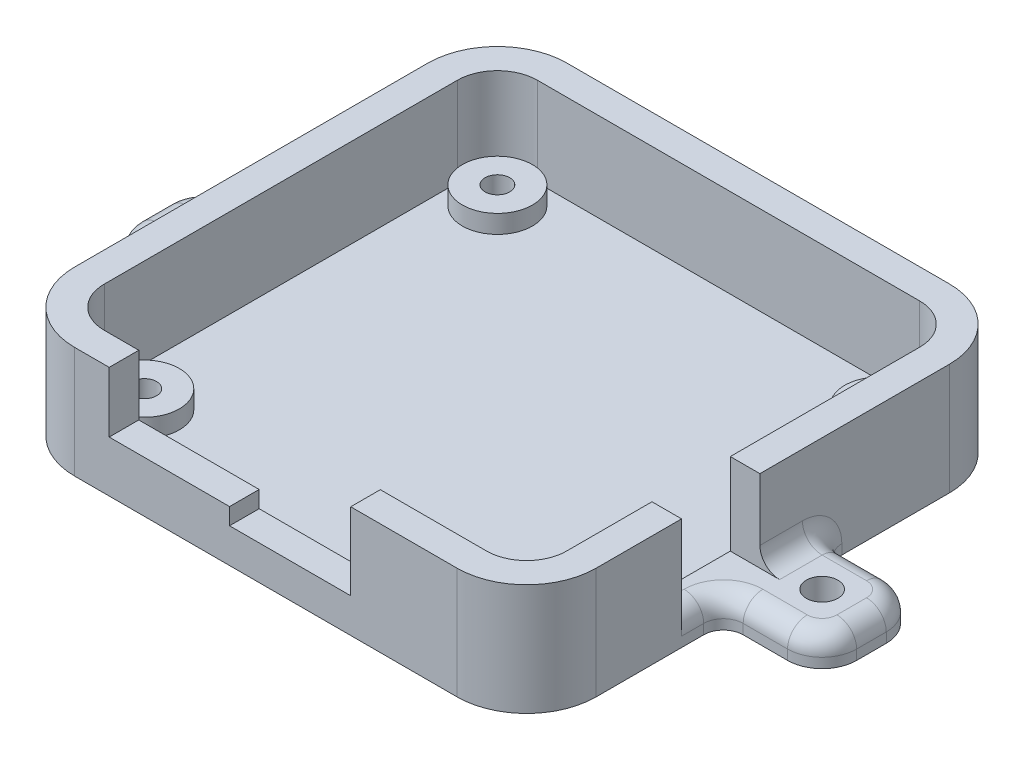
SolidWorks part; units mm, degrees
ref_plane "Front Plane" through (0, 0, 0) normal (0, 0, 1) x (1, 0, 0)
ref_plane "Top Plane" through (0, 0, 0) normal (0, 1, 0) x (1, 0, 0)
ref_plane "Right Plane" through (0, 0, 0) normal (1, 0, 0) x (0, 0, -1)
sketch "Sketch1" plane through (0, 0, 0) normal (0, 1, 0) x (1, 0, 0)
  line L0 (3.556, 0.5) -> (42.304, 0.5)
  line L1 (3.556, 0) -> (42.304, 0)
  line L2 (0, -3.556) -> (0, -39.344)
  line L3 (3.556, -42.9) -> (42.304, -42.9)
  line L4 (45.86, -3.556) -> (45.86, -39.344)
  line L5 (46.36, -3.556) -> (46.36, -39.344)
  line L6 (3.556, -43.4) -> (42.304, -43.4)
  line L7 (-0.5, -3.556) -> (-0.5, -39.344)
  line L8 (3.556, 3.5) -> (42.304, 3.5)
  line L9 (49.36, -3.556) -> (49.36, -39.344)
  line L10 (3.556, -46.4) -> (42.304, -46.4)
  line L11 (-3.5, -3.556) -> (-3.5, -39.344)
  arc A0 (42.304, 0) -> (45.86, -3.556) centre (42.304, -3.556) cw
  arc A1 (45.86, -39.344) -> (42.304, -42.9) centre (42.304, -39.344) cw
  arc A2 (3.556, -42.9) -> (0, -39.344) centre (3.556, -39.344) cw
  arc A3 (0, -3.556) -> (3.556, 0) centre (3.556, -3.556) cw
  circle A4 centre (3.556, -3.556) radius 1.25
  circle A5 centre (42.304, -3.556) radius 1.25
  circle A6 centre (42.304, -39.344) radius 1.25
  circle A7 centre (3.556, -39.344) radius 1.25
  arc A8 (42.304, 0.5) -> (46.36, -3.556) centre (42.304, -3.556) cw
  arc A9 (46.36, -39.344) -> (42.304, -43.4) centre (42.304, -39.344) cw
  arc A10 (3.556, -43.4) -> (-0.5, -39.344) centre (3.556, -39.344) cw
  arc A11 (-0.5, -3.556) -> (3.556, 0.5) centre (3.556, -3.556) cw
  arc A12 (42.304, 3.5) -> (49.36, -3.556) centre (42.304, -3.556) cw
  arc A13 (49.36, -39.344) -> (42.304, -46.4) centre (42.304, -39.344) cw
  arc A14 (3.556, -46.4) -> (-3.5, -39.344) centre (3.556, -39.344) cw
  arc A15 (-3.5, -3.556) -> (3.556, 3.5) centre (3.556, -3.556) cw
  circle A16 centre (3.556, -3.556) radius 3.55
  circle A17 centre (42.304, -3.556) radius 3.55
  circle A18 centre (42.304, -39.344) radius 3.55
  circle A19 centre (3.556, -39.344) radius 3.55
  point P8 (45.86, 0)
  point P13 (0, -42.9)
  point P16 (0, 0)
  dimension "D3" = 3.556
  dimension "D4" = 2.5
  dimension "D5" = 2.5
  dimension "D6" = 2.5
  dimension "D7" = 2.5
  dimension "D1" = 42.9
  dimension "D2" = 45.86
  dimension "D8" = 0.5
  dimension "D9" = 3
  dimension "D10" = 2.3
extrude "Boss-Extrude1" add sketch "Sketch1" along normal blind 2.3 contours A15 L11 A14 L10 A13 L9 A12 L8 L7 A11 L0 A8 L5 A9 L6 A10 | A11 L7 A10 L6 A9 L5 A8 L0 L2 A3 L1 A0 L4 A1 L3 A2 | A3 L2 A2 L3 A1 L4 A0 L1 A19 A18 A17 A16 | A18 A6 | A19 A7 | A16 A4 | A17 A5 region at (22.93, 0, -0.4358) region at (22.93, 0, 21.45) region at (22.93, 0, -2.7731) region at (0.1064, 0, 3.556) region at (38.8544, 0, 3.556) region at (38.8544, 0, 39.344) region at (0.1064, 0, 39.344)
extrude "Boss-Extrude2" add sketch "Sketch1<3>" along normal blind 1.85 from surface contours A16 A4 | A17 A5 | A18 A6 | A19 A7 region at (0.1064, 0, 3.556) region at (38.8544, 0, 3.556) region at (38.8544, 0, 39.344) region at (0.1064, 0, 39.344) starting at face at (22.93, 2.3, 21.45)
sketch "Sketch1<3>" plane through (0, 0, 0) normal (0, 1, 0) x (1, 0, 0) same geometry as "Sketch1"
extrude "Boss-Extrude3" add sketch "Sketch1<4>" along normal blind 9 from surface contours A15 L11 A14 L10 A13 L9 A12 L8 L7 A11 L0 A8 L5 A9 L6 A10 region at (22.93, 0, -2.7731) starting at face at (42.304, 2.3, 42.894)
sketch "Sketch1<4>" plane through (0, 0, 0) normal (0, 1, 0) x (1, 0, 0) same geometry as "Sketch1"
sketch "Sketch2" plane through (49.36, 0, 0) normal (1, 0, 0) x (0, 0, -1)
  line L0 (-3.556, 0) -> (-39.344, 0) construction
  line L1 (-30.694, 11.3) -> (-22.756, 11.3)
  line L2 (-30.694, 11.3) -> (-30.694, 3)
  line L3 (-30.694, 3) -> (-22.756, 3)
  line L4 (-22.756, 11.3) -> (-22.756, 3)
  line L5 (-39.344, 11.3) -> (-3.556, 11.3) construction
  line L6 (-39.344, 11.3) -> (-39.344, 0) construction
  line L7 (-3.556, 11.3) -> (-3.556, 0) construction
  dimension "D1" = 3
  dimension "D2" = 0
  dimension "D3" = 8.65
  dimension "D4" = 19.2
extrude "Cut-Extrude3" cut sketch "Sketch2" against normal up to next
sketch "Sketch3" plane through (0, 0, 46.4) normal (0, 0, 1) x (1, 0, 0)
  line L0 (3.556, 11.3) -> (3.556, 0) construction
  line L1 (7.056, 11.3) -> (20.104, 11.3)
  line L2 (7.056, 11.3) -> (7.056, 5.18)
  line L3 (7.056, 5.18) -> (20.104, 5.18)
  line L4 (20.104, 11.3) -> (20.104, 5.18)
  line L5 (42.304, 11.3) -> (42.304, 0) construction
  line L6 (42.304, 11.3) -> (3.556, 11.3) construction
  line L8 (3.556, 0) -> (42.304, 0) construction
  dimension "D1" = 3.5
  dimension "D2" = 22.2
  dimension "D3" = 0
  dimension "D4" = 5.18
extrude "Cut-Extrude4" cut sketch "Sketch3" against normal up to next
sketch "Sketch4" plane through (0, 0, 46.4) normal (0, 0, 1) x (1, 0, 0)
  line L0 (3.556, 0) -> (42.304, 0) construction
  line L1 (31.534, 11.3) -> (19.254, 11.3)
  line L2 (31.534, 11.3) -> (31.534, 3.49)
  line L3 (31.534, 3.49) -> (19.254, 3.49)
  line L4 (19.254, 11.3) -> (19.254, 3.49)
  line L5 (42.304, 11.3) -> (20.104, 11.3) construction
  line L6 (42.304, 11.3) -> (42.304, 0) construction
  dimension "D1" = 3.49
  dimension "D2" = 0
  dimension "D3" = 10.77
  dimension "D4" = 12.28
extrude "Cut-Extrude5" cut sketch "Sketch4" against normal up to next
sketch "Sketch5" plane through (0, 0, 0) normal (0, -1, 0) x (1, 0, 0)
  line L0 (-3.5, 3.556) -> (-3.5, 39.344) construction
  line L1 (-3.5, 16.45) -> (-10, 16.45)
  line L2 (-3.5, 16.45) -> (-3.5, 26.45)
  line L3 (-3.5, 26.45) -> (-10, 26.45)
  line L4 (-13.5, 19.95) -> (-13.5, 22.95)
  line L5 (49.36, 3.556) -> (49.36, 39.344) construction
  line L6 (49.36, 16.45) -> (55.86, 16.45)
  line L7 (49.36, 16.45) -> (49.36, 26.45)
  line L8 (49.36, 26.45) -> (55.86, 26.45)
  line L9 (59.36, 19.95) -> (59.36, 22.95)
  line L10 (3.556, -3.5) -> (42.304, -3.5) construction
  arc A0 (-10, 26.45) -> (-13.5, 22.95) centre (-10, 22.95) ccw
  arc A1 (-10, 16.45) -> (-13.5, 19.95) centre (-10, 19.95) cw
  arc A2 (55.86, 26.45) -> (59.36, 22.95) centre (55.86, 22.95) cw
  arc A3 (55.86, 16.45) -> (59.36, 19.95) centre (55.86, 19.95) ccw
  circle A4 centre (54.36, 21.45) radius 1.6
  circle A5 centre (-8.5, 21.45) radius 1.6
  point P16 (-13.5, 26.45)
  point P19 (-13.5, 16.45)
  point P24 (59.36, 16.45)
  dimension "D5" = 3.5
  dimension "D6" = 3.2
  dimension "D9" = 3.2
  dimension "D1" = 10
  dimension "D2" = 10
  dimension "D3" = 10
  dimension "D4" = 19.95
  dimension "D7" = 5
  dimension "D8" = 5
  dimension "D10" = 5
  dimension "D11" = 5
extrude "Boss-Extrude4" add sketch "Sketch5" against normal blind 3
fillet "Fillet1" radius 2 17 edges at (49.36, 3, 28.572) (-6.75, 3, 26.45) (-12.4749, 3, 25.4249) (-13.5, 3, 21.45) (-12.4749, 3, 17.4751) (52.61, 3, 16.45) (58.3349, 3, 17.4751) (59.36, 3, 21.45) (58.3349, 3, 25.4249) (-6.75, 3, 16.45) (52.61, 3, 26.45) (49.36, 1.5, 26.45) (49.36, 1.5, 16.45) (49.36, 3, 19.603) (-3.5, 1.5, 26.45) (-3.5, 1.5, 16.45) (-3.5, 3, 21.45)
